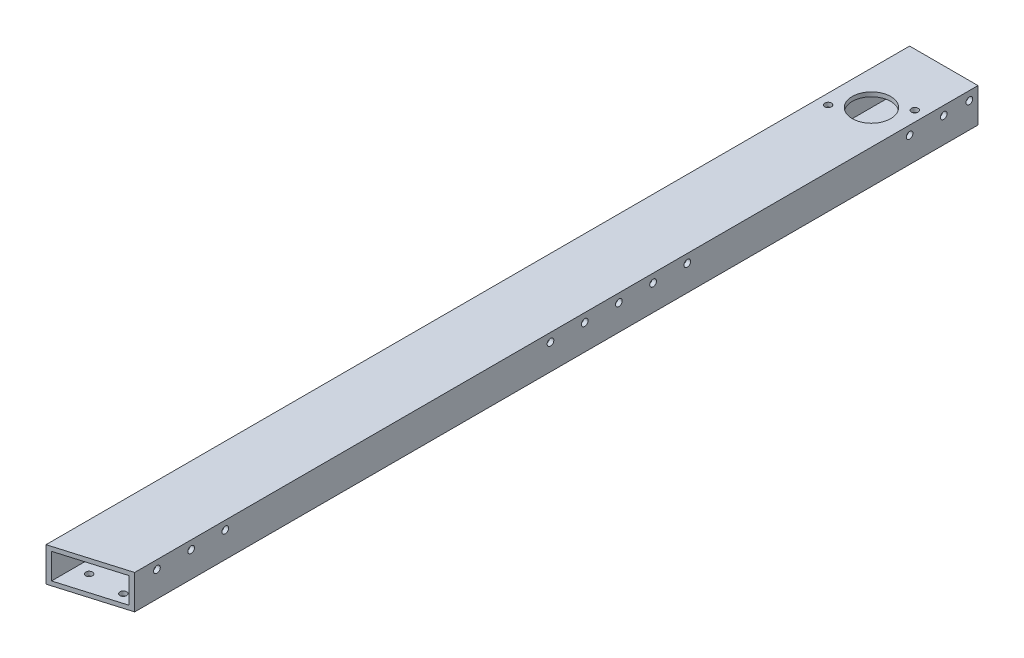
SolidWorks part; units mm, degrees
ref_plane "Front Plane" through (0, 0, 0) normal (0, 0, 1) x (1, 0, 0)
ref_plane "Top Plane" through (0, 0, 0) normal (0, 1, 0) x (1, 0, 0)
ref_plane "Right Plane" through (0, 0, 0) normal (1, 0, 0) x (0, 0, -1)
sketch "Sketch1" plane through (0, 0, 0) normal (0, 0, 1) x (1, 0, 0)
  line L0 (-22.225, 9.525) -> (22.225, 9.525)
  line L2 (-25.4, 12.7) -> (25.4, 12.7)
  line L3 (-25.4, 12.7) -> (-25.4, -12.7)
  line L4 (-25.4, -12.7) -> (25.4, -12.7)
  line L5 (25.4, 12.7) -> (25.4, -12.7)
  line L10 (22.225, 9.525) -> (22.225, -9.525)
  line L11 (-22.225, -9.525) -> (22.225, -9.525)
  line L12 (-22.225, 9.525) -> (-22.225, -9.525)
  point P12 (0, 12.7)
  point P14 (25.4, 0)
  dimension "Wall Thickness" = 3.175
  dimension "Outside Width" = 50.8
  dimension "Outside Height" = 25.4
  dimension "Inside Height" = 19.05
  dimension "Inside Width" = 44.45
sketch "Sketch2" plane through (0, 0, 0) normal (1, 0, 0) x (0, 0, -1)
  line L0 (320.675, 0) -> (-320.675, 0)
  point P4 (0, 0)
  point P7 (-320.675, 0)
  point P10 (320.675, 0)
  dimension "Length" = 641.35
sketch "Sketch3" plane through (0, 0, 0) normal (0, 0, 1) x (1, 0, 0)
  line L21 (25.4, 12.7) -> (-25.4, 12.7)
  line L22 (25.4, -12.7) -> (25.4, 12.7)
  line L23 (-25.4, -12.7) -> (25.4, -12.7)
  line L24 (-25.4, 12.7) -> (-25.4, -12.7)
  line L25 (25.4, 12.7) -> (-25.4, 12.7)
  line L26 (25.4, -12.7) -> (25.4, 12.7)
  line L27 (-25.4, -12.7) -> (25.4, -12.7)
  line L28 (-25.4, 12.7) -> (-25.4, -12.7)
  line L29 (22.225, 9.525) -> (-22.225, 9.525)
  line L30 (22.225, -9.525) -> (22.225, 9.525)
  line L31 (-22.225, -9.525) -> (22.225, -9.525)
  line L32 (-22.225, 9.525) -> (-22.225, -9.525)
  line L33 (22.225, 9.525) -> (-22.225, 9.525)
  line L34 (22.225, -9.525) -> (22.225, 9.525)
  line L35 (-22.225, -9.525) -> (22.225, -9.525)
  line L36 (-22.225, 9.525) -> (-22.225, -9.525)
  dimension "D1" = 0
  dimension "D2" = 0
extrude "Boss-Extrude1" add sketch "Sketch3" along normal up to vertex (320.675 mm away) and the other way up to vertex (320.675 mm away) up to point (0, 0, 320.675) other way up to point (0, 0, -320.675)
sketch "Drawing Reference" plane through (0, 0, 0) normal (1, 0, 0) x (0, 0, -1)
  line L0 (-320.675, 0) -> (320.675, 0) construction
  line L1 (0, -12.7) -> (0, 12.7) construction
  line L2 (-320.675, -12.7) -> (320.675, -12.7) construction
  line L5 (-320.675, 12.7) -> (320.675, 12.7) construction
  point P7 (-284.099, 0)
  point P8 (284.099, 0)
  dimension "D1" = 36.576
sketch "Sketch4" plane through (0, 12.7, 0) normal (0, 1, 0) x (1, 0, 0)
  line L0 (-25.4, -320.675) -> (25.4, -305.6274)
  line L1 (25.4, -320.675) -> (25.4, 320.675) construction
  line L2 (25.4, -320.675) -> (-25.4, -320.675)
  dimension "D1" = 16.5
extrude "Cut-Extrude1" cut sketch "Sketch4" against normal through all and the other way through all flip side to cut
sketch "Sketch8" plane through (0, 12.7, 0) normal (0, 1, 0) x (1, 0, 0)
  line L0 (0, 320.675) -> (0, 266.954) construction
  line L1 (25.4, 320.675) -> (-25.4, 320.675) construction
  circle A0 centre (0, 266.954) radius 14.2875
  dimension "D1" = 53.721
extrude "Cut-Extrude2" cut sketch "Sketch8" against normal through all
sketch "Sketch9" plane through (0, -12.7, 0) normal (0, -1, 0) x (1, 0, 0)
  line L0 (-12.7762, 284.753) -> (-12.7762, 301.263) construction
  line L1 (-12.7762, 301.263) -> (12.6238, 301.263) construction
  line L2 (12.6238, 301.263) -> (12.6238, 284.753) construction
  line L3 (12.6238, 284.753) -> (-12.7762, 284.753) construction
hole_wizard "#10 Clearance Hole1" positions "Sketch10" profile "Sketch11" hole size "#10" standard "ANSI Inch"
sketch "Sketch10" plane through (0, -12.7, 0) normal (0, -1, 0) x (-1, 0, 0)
  point P0 (-12.6238, -284.753)
  point P3 (12.7762, -284.753)
  point P6 (12.7762, -301.263)
  point P9 (-12.6238, -301.263)
sketch "Sketch11" plane through (12.6238, -12.7, 284.753) normal (1, 0, 0) x (0, 0, -1)
  line L0 (0, 0) -> (0, 6.5757)
  line L1 (0, 6.5757) -> (2.4892, 5.08)
  line L2 (2.4892, 5.08) -> (2.4892, 0)
  line L5 (2.4892, 0) -> (0, 0)
  line L10 (0, 6.5757) -> (-2.4892, 5.08) construction
  line L11 (0, -6.35) -> (0, 107.95) construction
  dimension "Hole Dia." = 4.9784
  dimension "Hole Depth" = 5.08
  dimension "Drill Angle" = 118
sketch "Sketch12" plane through (25.4, 0, 0) normal (1, 0, 0) x (0, 0, -1)
  line L0 (320.675, 533.4) -> (-305.6274, 533.4) construction
  line L1 (320.675, 520.7) -> (320.675, 546.1) construction
  line L2 (-305.6274, 546.1) -> (-305.6274, 520.7) construction
hole_wizard "#10 Clearance Hole2" positions "Sketch13" profile "Sketch14" hole size "#10" standard "ANSI Inch"
sketch "Sketch13" plane through (25.4, 0, 0) normal (1, 0, 0) x (0, 0, -1)
  point P0 (314.2868, 6.1483)
  point P3 (295.2368, 6.1483)
  point P6 (269.875, 6.1483)
sketch "Sketch14" plane through (25.4, 6.1483, -314.2868) normal (0, 1, 0) x (0, 0, -1)
  line L0 (0, 0) -> (0, 4.7977)
  line L1 (0, 4.7977) -> (2.4892, 3.302)
  line L2 (2.4892, 3.302) -> (2.4892, 0)
  line L5 (2.4892, 0) -> (0, 0)
  line L10 (0, 4.7977) -> (-2.4892, 3.302) construction
  line L11 (0, -6.35) -> (0, 107.95) construction
  dimension "Hole Dia." = 4.9784
  dimension "Hole Depth" = 3.302
  dimension "Drill Angle" = 118
hole_wizard "#10 Clearance Hole3" positions "Sketch15" profile "Sketch16" hole size "#10" standard "ANSI Inch" end condition through all
sketch "Sketch15" plane through (25.4, 0, 0) normal (1, 0, 0) x (0, 0, -1)
  point P0 (104.775, 6.35)
  point P3 (79.375, 6.35)
  point P6 (53.975, 6.35)
  point P9 (28.575, 6.35)
  point P12 (3.175, 6.35)
  point P24 (-289.0885, 6.3882)
  point P27 (-263.6885, 6.3882)
  point P30 (-238.3267, 6.3882)
sketch "Sketch16" plane through (25.4, 6.35, -104.775) normal (0, 1, 0) x (0, 0, -1)
  line L0 (0, 0) -> (0, 50.8)
  line L1 (0, 50.8) -> (2.4892, 50.8)
  line L2 (2.4892, 50.8) -> (2.4892, 0)
  line L5 (2.4892, 0) -> (0, 0)
  line L11 (0, -6.35) -> (0, 107.95) construction
  dimension "Thru Hole Dia." = 4.9784
  dimension "Thru Hole Depth" = 50.8
sketch "Sketch18" plane through (0, 12.7, 0) normal (0, 1, 0) x (1, 0, 0)
  line L0 (17.786, 281.371) -> (-17.786, 252.537) construction
hole_wizard "#10 Clearance Hole4" positions "Sketch19" profile "Sketch20" hole size "#10" standard "ANSI Inch" end condition through all
sketch "Sketch19" plane through (0, 12.7, 0) normal (0, 1, 0) x (1, 0, 0)
  point P0 (-17.786, 252.537)
  point P3 (17.786, 281.371)
sketch "Sketch20" plane through (-17.786, 12.7, -252.537) normal (1, 0, 0) x (0, 0, 1)
  line L0 (0, 0) -> (0, 25.4)
  line L1 (0, 25.4) -> (5.2197, 25.4)
  line L2 (2.4892, 22.2589) -> (2.4892, 0)
  line L5 (2.4892, 0) -> (0, 0)
  line L7 (5.2197, 25.4) -> (2.4892, 22.2589)
  line L8 (-5.2197, 25.4) -> (-2.4892, 22.2589) construction
  line L11 (0, -6.35) -> (0, 107.95) construction
  dimension "Thru Hole Dia." = 4.9784
  dimension "Thru Hole Depth" = 25.4
  dimension "Far C'Sink Dia." = 10.4394
  dimension "Far C'Sink Angle" = 82
equation "\"D1@Drawing Reference\"=\"Outside Width@Sketch1\" * 0.72"
